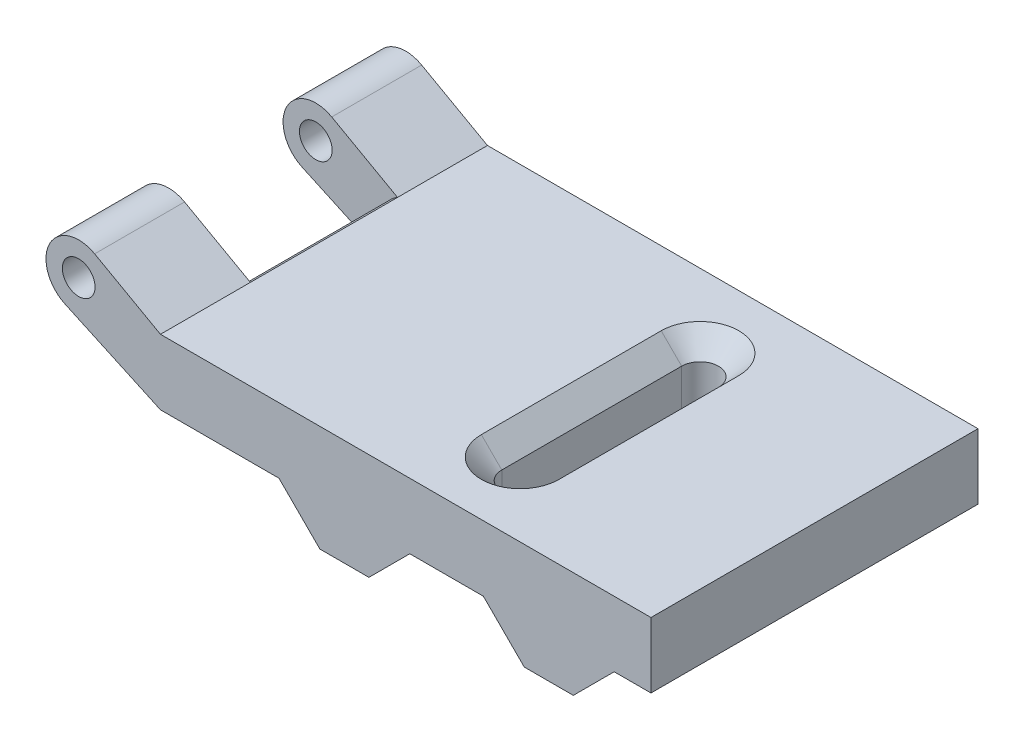
SolidWorks part; units mm, degrees
ref_plane "Top Plane" through (0, 0, 0) normal (0, 0, 1) x (1, 0, 0)
ref_plane "Right Plane" through (0, 0, 0) normal (0, 1, 0) x (1, 0, 0)
ref_plane "Front Plane" through (0, 0, 0) normal (1, 0, 0) x (0, 0, -1)
sketch "Sketch1" plane through (0, 0, 0) normal (0, 0, 1) x (1, 0, 0)
  line L0 (10, -9) -> (24.5, -9)
  line L1 (24.5, -9) -> (29.5, -14)
  line L2 (29.5, -14) -> (35.5, -14)
  line L3 (35.5, -14) -> (40.5, -9)
  line L4 (40.5, -9) -> (49.5, -9)
  line L5 (49.5, -9) -> (54.5, -14)
  line L6 (54.5, -14) -> (60.5, -14)
  line L7 (60.5, -14) -> (65.5, -9)
  line L8 (65.5, -9) -> (70, -9)
  line L9 (70, -9) -> (70, -1)
  line L10 (70, -1) -> (10, -1)
  line L11 (20, -9) -> (20, -5) construction
  line L12 (20, -5) -> (70, -5) construction
  line L13 (45, -5) -> (45, -9) construction
  line L14 (45, -7) -> (70, -7) construction
  line L15 (57.5, -14) -> (57.5, -7) construction
  line L16 (10, -9) -> (10, -1) construction
  line L17 (-1.6709, -3.6343) -> (10, -9)
  line L18 (10, -1) -> (1.9493, 3.4929)
  arc A0 (1.9493, 3.4929) -> (-1.6709, -3.6343) centre (0, 0) ccw
  arc A1 (-1.6709, -3.6343) -> (1.9493, 3.4929) centre (0, 0) ccw construction
  circle A2 centre (0, 0) radius 2
  point P26 (14.2873, -4)
  point P27 (14.0927, -4)
  point P28 (13.7369, -4)
  point P29 (-2.1921, -3.3459)
  point P30 (8.5771, -7.3496)
  dimension "D7" = 4
  dimension "D8" = 4
  dimension "D1" = 135
  dimension "D2" = 5
  dimension "D3" = 8
  dimension "D4" = 50
  dimension "D5" = 6
  dimension "D6" = 20
  dimension "D9" = 5
  dimension "D10" = 10
extrude "Boss-Extrude1" add sketch "Sketch1" along normal blind 40
sketch "Sketch2" plane through (0, -9, 0) normal (0, -1, 0) x (1, 0, 0)
  line L0 (45, 31) -> (45, 9) construction
  line L1 (47.25, 31) -> (47.25, 9)
  line L2 (42.75, 31) -> (42.75, 9)
  line L3 (45, 31) -> (45, 40) construction
  line L4 (40.5, 40) -> (49.5, 40) construction
  line L5 (45, 9) -> (45, 0) construction
  line L6 (40.5, 0) -> (49.5, 0) construction
  arc A0 (47.25, 31) -> (42.75, 31) centre (45, 31) ccw
  arc A1 (42.75, 9) -> (47.25, 9) centre (45, 9) ccw
  point P2 (45, 20)
  point P15 (65, 31.6347)
  dimension "D1" = 4.5
  dimension "D2" = 22
extrude "Cut-Extrude1" cut sketch "Sketch2" against normal through all
chamfer "Chamfer1" distance 2.5 angle 45 4 edges at (47.25, -1, 20) (45, -1, 33.25) (45, -1, 6.75) (42.75, -1, 20)
sketch "Sketch3" plane through (0, -9, 0) normal (0, -1, 0) x (1, 0, 0)
  line L0 (-4, 40) -> (-4, 0) construction
  line L1 (-4, 29) -> (8, 29)
  line L2 (-4, 29) -> (-4, 11)
  line L3 (-4, 11) -> (8, 11)
  line L4 (8, 29) -> (8, 11)
  point P4 (-4, 20)
  dimension "D1" = 18
  dimension "D2" = 12
extrude "Cut-Extrude2" cut sketch "Sketch3" against normal through all
fillet "Fillet1" radius 4 2 edges at (8, 0.1161, 20) (8, -8.0805, 20)
